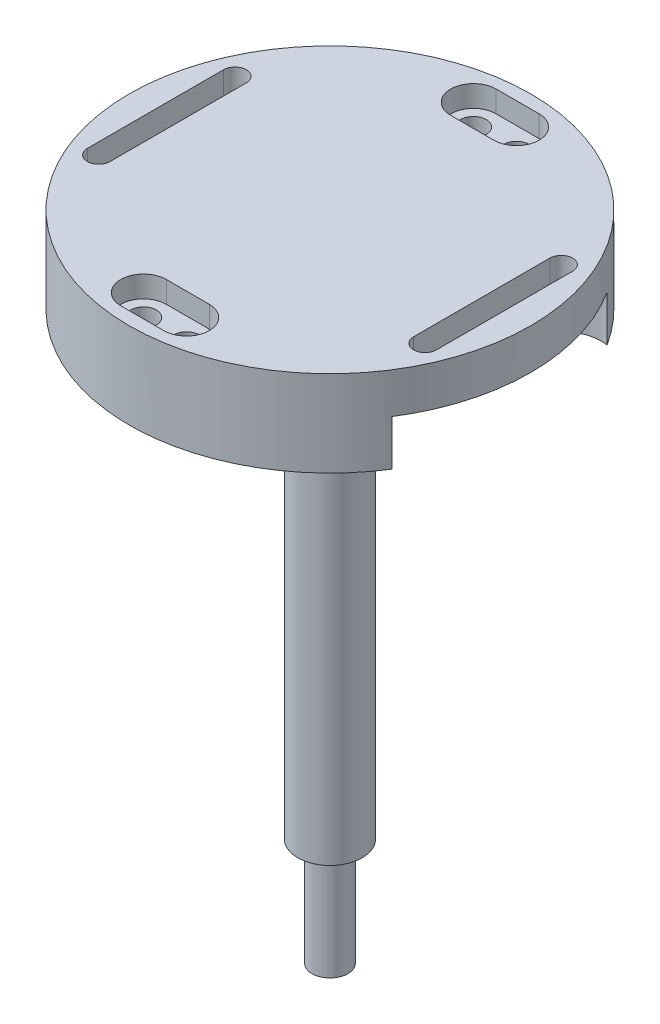
SolidWorks part; units mm, degrees
ref_plane "Front Plane" through (0, 0, 0) normal (0, 0, 1) x (1, 0, 0)
ref_plane "Top Plane" through (0, 0, 0) normal (0, 1, 0) x (1, 0, 0)
ref_plane "Right Plane" through (0, 0, 0) normal (1, 0, 0) x (0, 0, -1)
sketch "Sketch1" plane through (0, 0, 0) normal (0, 0, 1) x (1, 0, 0)
  line L0 (0, 0) -> (0, 91) construction
  line L1 (0, 91) -> (28, 91)
  line L2 (28, 91) -> (28, 79)
  line L3 (28, 79) -> (15, 79)
  line L4 (15, 79) -> (15, 80)
  line L5 (15, 80) -> (4.5, 80)
  line L6 (4.5, 80) -> (4.5, 15)
  line L7 (4.5, 15) -> (2.5, 15)
  line L8 (2.5, 15) -> (2.5, 0)
  line L9 (2.5, 0) -> (0, 0)
  line L10 (0, 0) -> (0, 91)
  dimension "D1" = 79
  dimension "D2" = 5
  dimension "D3" = 9
  dimension "D4" = 1
  dimension "D5" = 30
  dimension "D6" = 12
  dimension "D7" = 56
  dimension "D8" = 15
revolve "Revolve1" add sketch "Sketch1" angle 360 about L0
hole_wizard "CBORE for M3 SHCS1" positions "Sketch2" profile "Sketch3" counterbore size "M3" standard "ANSI Metric" end condition through all
sketch "Sketch2" plane through (0, 91, 0) normal (0, 1, 0) x (1, 0, 0)
  line L0 (0, 0) -> (0, 23) construction
  line L1 (0, 23) -> (3, 23) construction
  line L3 (0, 23) -> (-3, 23) construction
  line L5 (-3, -23) -> (0, -23) construction
  line L6 (0, -23) -> (0, 0) construction
  line L8 (0, -23) -> (3, -23) construction
  point P0 (3, 23)
  point P11 (-3, 23)
  point P14 (-3, -23)
  point P21 (3, -23)
  dimension "D1" = 46
  dimension "D2" = 6
sketch "Sketch3" plane through (3, 91, -23) normal (1, 0, 0) x (0, 0, 1)
  line L0 (0, 0) -> (0, 91)
  line L1 (0, 91) -> (1.8, 91)
  line L3 (1.8, 91) -> (1.8, 3)
  line L4 (1.8, 3) -> (3.175, 3)
  line L5 (3.175, 3) -> (3.175, 0)
  line L7 (3.175, 0) -> (0, 0)
  line L11 (0, -6.35) -> (0, 107.95) construction
  dimension "Thru Hole Dia." = 3.6
  dimension "Thru Hole Depth" = 91
  dimension "C'Bore Dia." = 6.35
  dimension "C'Bore Depth" = 3
sketch "Sketch4" plane through (0, 88, 0) normal (0, 1, 0) x (1, 0, 0)
  line L0 (-3, 23) -> (3, 23) construction
  line L1 (-3, 26.175) -> (3, 26.175)
  line L2 (-3, 19.825) -> (3, 19.825)
  line L3 (-3, -23) -> (3, -23) construction
  line L4 (-3, -19.825) -> (3, -19.825)
  line L5 (-3, -26.175) -> (3, -26.175)
  arc A0 (-3, 26.175) -> (-3, 19.825) centre (-3, 23) ccw
  arc A1 (3, 19.825) -> (3, 26.175) centre (3, 23) ccw
  arc A2 (0, 21.9605) -> (0, 24.0395) centre (3, 23) ccw construction
  arc A3 (-3, -19.825) -> (-3, -26.175) centre (-3, -23) ccw
  arc A4 (3, -26.175) -> (3, -19.825) centre (3, -23) ccw
  arc A5 (0, -21.9605) -> (0, -24.0395) centre (-3, -23) ccw construction
  point P4 (0, 23)
  point P16 (0, -23)
extrude "Cut-Extrude1" cut sketch "Sketch4" along normal through all
sketch "Sketch5" plane through (0, 91, 0) normal (0, 1, 0) x (1, 0, 0)
  line L0 (-22.75, -9.5) -> (-22.75, 9.5) construction
  line L1 (-24.3375, -9.5) -> (-24.3375, 9.5)
  line L2 (-21.1625, -9.5) -> (-21.1625, 9.5)
  arc A0 (-24.3375, -9.5) -> (-21.1625, -9.5) centre (-22.75, -9.5) ccw
  arc A1 (-21.1625, 9.5) -> (-24.3375, 9.5) centre (-22.75, 9.5) ccw
  point P2 (-22.75, 0)
  dimension "D1" = 22.75
  dimension "D2" = 19
  dimension "D3" = 3.175
extrude "Cut-Extrude2" cut sketch "Sketch5" against normal through all
mirror "Mirror1" about plane through (0, 0, 0) normal (1, 0, 0) of "Cut-Extrude2"
sketch "Sketch7" plane through (0, 79, 0) normal (0, -1, 0) x (1, 0, 0)
  line L0 (21.1625, -9.5) -> (21.1625, 9.5)
  line L1 (21.1625, -9.5) -> (21.1625, 9.5) construction
  line L2 (24.3375, 9.5) -> (24.3375, -9.5)
  line L3 (24.3375, 9.5) -> (24.3375, -9.5) construction
  line L4 (-21.1625, -9.5) -> (-21.1625, 9.5)
  line L5 (-21.1625, -9.5) -> (-21.1625, 9.5) construction
  line L6 (-24.3375, 9.5) -> (-24.3375, -9.5)
  line L7 (-24.3375, 9.5) -> (-24.3375, -9.5) construction
  line L8 (28.3062, 9.5) -> (28.3062, -9.5)
  line L9 (17.1938, -9.5) -> (17.1938, 9.5)
  line L10 (-17.1938, -9.5) -> (-17.1938, 9.5)
  line L11 (-28.3062, 9.5) -> (-28.3063, -9.5)
  arc A0 (24.3375, 9.5) -> (21.1625, 9.5) centre (22.75, 9.5) ccw
  arc A1 (24.3375, 9.5) -> (21.1625, 9.5) centre (22.75, 9.5) ccw construction
  arc A2 (21.1625, -9.5) -> (24.3375, -9.5) centre (22.75, -9.5) ccw
  arc A3 (21.1625, -9.5) -> (24.3375, -9.5) centre (22.75, -9.5) ccw construction
  arc A4 (-24.3375, -9.5) -> (-21.1625, -9.5) centre (-22.75, -9.5) ccw
  arc A5 (-24.3375, -9.5) -> (-21.1625, -9.5) centre (-22.75, -9.5) ccw construction
  arc A6 (-21.1625, 9.5) -> (-24.3375, 9.5) centre (-22.75, 9.5) ccw
  arc A7 (-21.1625, 9.5) -> (-24.3375, 9.5) centre (-22.75, 9.5) ccw construction
  arc A8 (17.1938, -9.5) -> (28.3062, -9.5) centre (22.75, -9.5) ccw
  arc A9 (28.3062, 9.5) -> (17.1938, 9.5) centre (22.75, 9.5) ccw
  arc A10 (-17.1938, 9.5) -> (-28.3062, 9.5) centre (-22.75, 9.5) ccw
  arc A11 (-28.3063, -9.5) -> (-17.1938, -9.5) centre (-22.75, -9.5) ccw
  dimension "D1" = 11.1125
  dimension "D2" = 11.1125
extrude "Cut-Extrude3" cut sketch "Sketch7" against normal blind 6.35
sketch "Sketch9" plane through (0, 80, 0) normal (0, -1, 0) x (1, 0, 0)
  circle A0 centre (0, 0) radius 4.5 construction
  circle A1 centre (0, 0) radius 4.5
equation "\"mm\"=0.1"
